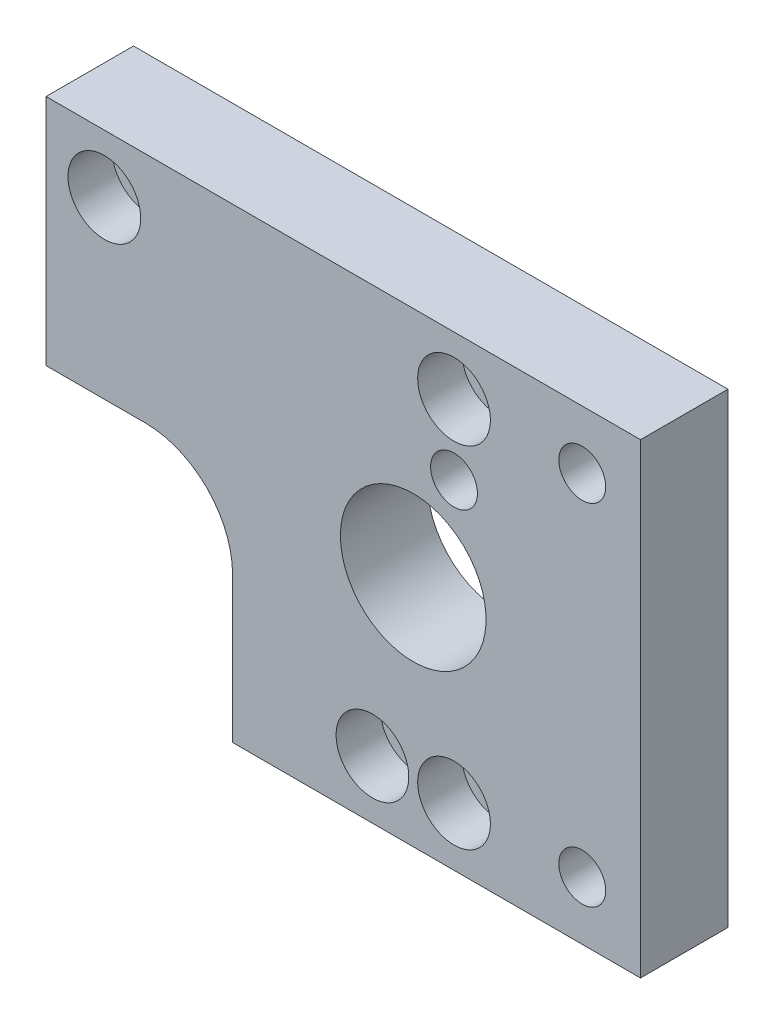
SolidWorks part; units mm, degrees
material "1060 Alloy"
ref_plane "Front Plane" through (0, 0, 0) normal (0, 0, 1) x (1, 0, 0)
ref_plane "Top Plane" through (0, 0, 0) normal (0, 1, 0) x (1, 0, 0)
ref_plane "Right Plane" through (0, 0, 0) normal (1, 0, 0) x (0, 0, -1)
sketch "Sketch1" plane through (0, 0, 0) normal (0, 0, 1) x (1, 0, 0)
  line L0 (0, 25.4) -> (0, 0) construction
  line L1 (-25.4, -25.4) -> (39.37, -25.4)
  line L2 (-25.4, -25.4) -> (-25.4, 25.4)
  line L3 (-25.4, 25.4) -> (39.37, 25.4)
  line L4 (39.37, -25.4) -> (39.37, 25.4)
  line L7 (39.37, 0) -> (-25.4, 0) construction
  circle A0 centre (-19.05, 19.05) radius 2.5527
  circle A1 centre (19.05, 19.05) radius 2.5527
  circle A2 centre (19.05, -19.05) radius 2.5527
  circle A3 centre (10.16, -19.05) radius 2.5527
  circle A4 centre (14.605, 0) radius 7.9375
  point P0 (0, 0)
  dimension "D3" = 5.1054
  dimension "D7" = 15.875
  dimension "D1" = 64.77
  dimension "D2" = 50.8
  dimension "D4" = 38.1
  dimension "D5" = 6.35
  dimension "D6" = 4.445
  dimension "D8" = 38.1
  dimension "D9" = 8.89
  dimension "D10" = 25.4
extrude "Boss-Extrude1" add sketch "Sketch1" along normal blind 9.525
hole_wizard "#7 (0.201) Diameter Hole1" positions "Sketch4" profile "Sketch5" hole size "#7" standard "ANSI Inch"
sketch "Sketch4" plane through (-24.7212, -12.8643, 0) normal (0, 0, 1) x (1, 0, 0)
  line L0 (64.0912, -12.5357) -> (64.0912, 38.2643) construction
  line L2 (64.0912, 38.2643) -> (-0.6788, 38.2643) construction
  circle A5 centre (43.7712, -6.1857) radius 2.5527 construction
  circle A6 centre (43.7712, -6.1857) radius 2.5527 construction
  circle A7 centre (43.7712, 31.9143) radius 2.5527 construction
  circle A8 centre (43.7712, 31.9143) radius 2.5527 construction
  point P0 (57.7412, -6.1857)
  point P7 (57.7412, 31.9143)
  point P33 (43.7712, 24.2943)
  dimension "D3" = 7.62
  dimension "D1" = 6.35
  dimension "D2" = 6.35
sketch "Sketch5" plane through (33.02, -19.05, 0) normal (1, 0, 0) x (0, 1, 0)
  line L0 (0, 0) -> (0, 71.6378)
  line L1 (0, 71.6378) -> (2.5527, 70.104)
  line L2 (2.5527, 70.104) -> (2.5527, 0)
  line L5 (2.5527, 0) -> (0, 0)
  line L10 (0, 71.6378) -> (-2.5527, 70.104) construction
  line L11 (0, -6.35) -> (0, 107.95) construction
  dimension "Hole Dia." = 5.1054
  dimension "Hole Depth" = 70.104
  dimension "Drill Angle" = 118
sketch "Sketch6" plane through (0, 0, 9.525) normal (0, 0, -1) x (-1, 0, 0)
  circle A0 centre (-19.05, 19.05) radius 3.9624
  circle A3 centre (-19.05, -19.05) radius 3.9624
  circle A4 centre (-10.16, -19.05) radius 3.9624
  circle A5 centre (19.05, 19.05) radius 3.9624
  dimension "D1" = 7.9248
extrude "Cut-Extrude1" cut sketch "Sketch6" along normal blind 4.826
sketch "Sketch7" plane through (0, 0, 0) normal (0, 0, -1) x (-1, 0, 0)
  line L1 (25.4, -25.4) -> (5.08, -25.4)
  line L2 (25.4, -25.4) -> (25.4, 0)
  line L3 (25.4, 0) -> (5.08, 0)
  line L4 (5.08, -25.4) -> (5.08, 0)
  dimension "D1" = 20.32
extrude "Cut-Extrude2" cut sketch "Sketch7" against normal through all
fillet "Fillet2" radius 9.525 1 edges at (-5.08, 0, 4.7625)
